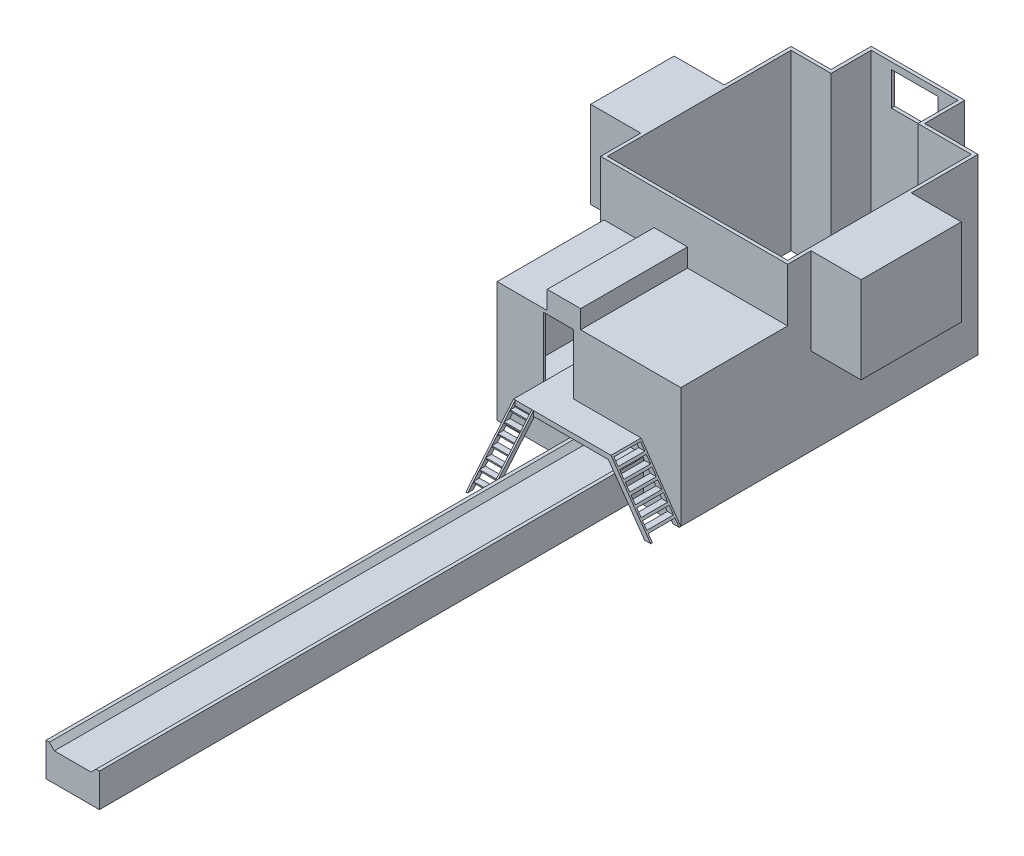
SolidWorks part; units mm, degrees
ref_plane "Alzado" through (0, 0, 0) normal (0, 0, 1) x (1, 0, 0)
ref_plane "Planta" through (0, 0, 0) normal (0, 1, 0) x (1, 0, 0)
ref_plane "Vista lateral" through (0, 0, 0) normal (1, 0, 0) x (0, 0, -1)
sketch "Croquis1" plane through (0, 0, 0) normal (0, 1, 0) x (1, 0, 0)
  line L0 (0, 0) -> (0, 3200)
  line L1 (0, 3200) -> (-100, 3200)
  line L2 (-100, 3200) -> (-100, 4400)
  line L3 (-100, 8900) -> (500, 8900)
  line L4 (500, 8900) -> (1100, 8900)
  line L5 (1100, 8900) -> (1100, 10102.7991)
  line L6 (1100, 10102.7991) -> (3900, 10102.7991)
  line L7 (3900, 8900) -> (5500, 8900)
  line L8 (5500, 8900) -> (5500, 6900)
  line L9 (5500, 0) -> (0, 0)
  line L10 (-100, 4400) -> (-1600, 4400)
  line L11 (-1600, 4400) -> (-1600, 6900)
  line L12 (-1600, 6900) -> (-100, 6900)
  line L13 (-100, 6900) -> (-100, 8900)
  line L14 (5500, 6900) -> (7000, 6900)
  line L15 (7000, 6900) -> (7000, 3900)
  line L16 (7000, 3900) -> (5500, 3900)
  line L17 (5500, 3900) -> (5500, 0)
  line L18 (3900, 10102.7991) -> (3900, 8900)
  dimension "D1" = 5500
  dimension "D2" = 3200
  dimension "D3" = 100
  dimension "D4" = 5700
  dimension "D5" = 1600
  dimension "D6" = 2800
  dimension "D8" = 1200
  dimension "D9" = 2000
  dimension "D10" = 1500
  dimension "D11" = 1500
  dimension "D12" = 2000
  dimension "D13" = 3900
extrude "Saliente-Extruir1" add sketch "Croquis1" along normal blind 5200
sketch "Croquis2" plane through (0, 0, 0) normal (0, 0, 1) x (1, 0, 0)
  line L0 (5500, 5200) -> (5500, 0) construction
  line L1 (0, 5200) -> (5500, 5200)
  line L2 (0, 5200) -> (0, 3600)
  line L3 (0, 3600) -> (5500, 3600)
  line L4 (5500, 5200) -> (5500, 3600)
  dimension "D1" = 1600
extrude "Cortar-Extruir1" cut sketch "Croquis2" against normal up to surface (3200 mm away) up to face at (-50, 2600, -3200)
sketch "Croquis3" plane through (-1600, 0, 0) normal (-1, 0, 0) x (0, 0, 1)
  line L0 (-4400, 5200) -> (-4400, 0) construction
  line L1 (-6900, 0) -> (-4400, 0)
  line L2 (-6900, 0) -> (-6900, 2600)
  line L3 (-6900, 2600) -> (-4400, 2600)
  line L4 (-4400, 0) -> (-4400, 2600)
extrude "Cortar-Extruir2" cut sketch "Croquis3" against normal up to surface (1500 mm away) up to face at (-100, 2600, -3800)
sketch "Croquis4" plane through (7000, 0, 0) normal (1, 0, 0) x (0, 0, -1)
  line L0 (6900, 5200) -> (6900, 0) construction
  line L1 (3900, 0) -> (6900, 0)
  line L2 (3900, 0) -> (3900, 2600)
  line L3 (3900, 2600) -> (6900, 2600)
  line L4 (6900, 0) -> (6900, 2600)
extrude "Cortar-Extruir3" cut sketch "Croquis4" against normal up to surface (1500 mm away) up to face at (5500, 2600, -7900)
sketch "Croquis5" plane through (0, 0, 0) normal (0, 0, 1) x (1, 0, 0)
  line L0 (0, 0) -> (1190.3528, 1700)
  line L1 (1190.3528, 1700) -> (4309.6472, 1700)
  line L2 (4309.6472, 1700) -> (5500, 0)
  line L3 (0, 0) -> (5500, 0) construction
  line L4 (5500, 3600) -> (5500, 0) construction
  line L5 (0, 3600) -> (0, 0) construction
  line L6 (0, 0) -> (183.1162, 0)
  line L7 (183.1162, 0) -> (1268.4379, 1550)
  line L8 (5500, 0) -> (5316.8838, 0)
  line L9 (5316.8838, 0) -> (4231.5621, 1550)
  line L10 (1268.4379, 1550) -> (4231.5621, 1550)
  dimension "D1" = 1700
  dimension "D2" = 35
  dimension "D3" = 35
  dimension "D4" = 150
  dimension "D5" = 150
  dimension "D6" = 150
extrude "Saliente-Extruir2" add sketch "Croquis5" along normal blind 900
sketch "Croquis6" plane through (0, 0, 0) normal (-1, 0, 0) x (0, 0, 1)
  line L0 (900, 0) -> (0, 0) construction
  line L1 (50, 0) -> (850, 0)
  line L2 (50, 0) -> (50, 180)
  line L3 (50, 180) -> (850, 180)
  line L4 (850, 0) -> (850, 180)
  line L5 (900, 1700) -> (900, 0) construction
  line L6 (0, 3600) -> (0, 0) construction
  dimension "D1" = 50
  dimension "D2" = 50
  dimension "D3" = 180
extrude "Cortar-Extruir4" cut sketch "Croquis6" against normal up to surface (5500 mm away) up to face at (5500, 3320, -4580)
sketch "Croquis7" plane through (0, 0, 0) normal (-1, 0, 0) x (0, 0, 1)
  line L0 (50, 180) -> (850, 180) construction
  line L1 (50, 240) -> (850, 240)
  line L2 (50, 240) -> (50, 425)
  line L3 (50, 425) -> (850, 425)
  line L4 (850, 240) -> (850, 425)
  line L6 (50, 485) -> (850, 485)
  line L7 (50, 485) -> (50, 670)
  line L8 (50, 670) -> (850, 670)
  line L9 (850, 485) -> (850, 670)
  line L10 (50, 730) -> (850, 730)
  line L11 (50, 730) -> (50, 915)
  line L12 (50, 915) -> (850, 915)
  line L13 (850, 730) -> (850, 915)
  line L14 (50, 975) -> (850, 975)
  line L15 (50, 975) -> (50, 1160)
  line L16 (50, 1160) -> (850, 1160)
  line L17 (850, 975) -> (850, 1160)
  line L18 (50, 1220) -> (850, 1220)
  line L19 (50, 1220) -> (50, 1405)
  line L20 (50, 1405) -> (850, 1405)
  line L21 (850, 1220) -> (850, 1405)
  line L22 (50, 1465) -> (850, 1465)
  line L23 (50, 1465) -> (50, 1650)
  line L24 (50, 1650) -> (850, 1650)
  line L25 (850, 1465) -> (850, 1650)
  dimension "D1" = 60
  dimension "D2" = 185
  dimension "D3" = 185
  dimension "D4" = 60
  dimension "D5" = 185
  dimension "D6" = 60
  dimension "D7" = 60
  dimension "D8" = 185
  dimension "D9" = 60
  dimension "D10" = 185
  dimension "D11" = 60
  dimension "D12" = 185
extrude "Cortar-Extruir5" cut sketch "Croquis7" against normal up to surface (5500 mm away) up to face at (5500, 3320, -4580)
sketch "Croquis8" plane through (0, 0, 0) normal (0, 0, 1) x (1, 0, 0)
  line L0 (4309.6472, 1700) -> (1190.3528, 1700) construction
  line L1 (1390.3528, 1700) -> (2290.3528, 1700)
  line L2 (1390.3528, 1700) -> (1390.3528, 3500)
  line L3 (1390.3528, 3500) -> (2290.3528, 3500)
  line L4 (2290.3528, 1700) -> (2290.3528, 3500)
  dimension "D1" = 1800
  dimension "D2" = 200
  dimension "D3" = 900
extrude "Cortar-Extruir6" cut sketch "Croquis8" against normal up to surface (3200 mm away) up to face at (1800, 2933.3333, -3200)
sketch "Croquis9" plane through (0, 0, 0) normal (0, -1, 0) x (1, 0, 0)
  line L0 (0, -3200) -> (0, 0) construction
  line L1 (50.8, -3149.2) -> (5449.2, -3149.2)
  line L2 (50.8, -3149.2) -> (50.8, -51.6)
  line L3 (50.8, -51.6) -> (5449.2, -51.6)
  line L4 (5449.2, -3149.2) -> (5449.2, -51.6)
  line L5 (183.1162, 50) -> (0, 50) construction
  line L6 (5500, 0) -> (5500, -8900) construction
  dimension "D1" = 50.8
  dimension "D2" = 101.6
  dimension "D3" = 50.8
  dimension "D4" = 50.8
extrude "Cortar-Extruir7" cut sketch "Croquis9" against normal blind 3500
sketch "Croquis10" plane through (0, 0, 900) normal (0, 0, 1) x (1, 0, 0)
  line L1 (1390.3528, 1700) -> (2290.3528, 1700)
  line L2 (1390.3528, 1700) -> (1390.3528, 1600)
  line L3 (1390.3528, 1600) -> (2290.3528, 1600)
  line L4 (2290.3528, 1700) -> (2290.3528, 1600)
  dimension "D1" = 100
extrude "Saliente-Extruir3" add sketch "Croquis10" against normal up to surface (4049.2 mm away) up to face at (2295.1764, 2175, -3149.2)
sketch "Croquis11" plane through (0, 0, 0) normal (0, 0, 1) x (1, 0, 0)
  line L0 (183.1162, 0) -> (5316.8838, 0) construction
  line L1 (2190, 0) -> (4390, 0)
  line L2 (2190, 0) -> (2190, 1300)
  line L3 (2190, 1300) -> (4390, 1300)
  line L4 (4390, 0) -> (4390, 1300)
  line L5 (5500, 3600) -> (5500, 0) construction
  dimension "D1" = 1110
  dimension "D2" = 2200
  dimension "D3" = 1300
extrude "Cortar-Extruir8" cut sketch "Croquis11" against normal up to surface (3149.2 mm away) up to face at (2204.2117, 2060, -3149.2)
sketch "Croquis12" plane through (0, 0, 0) normal (0, -1, 0) x (1, 0, 0)
  line L0 (50.8, -51.6) -> (50.8, -3149.2) construction
  line L1 (50.8, -1849.2) -> (5449.2, -1849.2)
  line L2 (50.8, -1849.2) -> (50.8, -549.2)
  line L3 (50.8, -549.2) -> (5449.2, -549.2)
  line L4 (5449.2, -1849.2) -> (5449.2, -549.2)
  line L5 (5449.2, -3149.2) -> (5449.2, -51.6) construction
  line L6 (50.8, -3149.2) -> (5449.2, -3149.2) construction
  dimension "D1" = 1300
  dimension "D2" = 1300
extrude "Saliente-Extruir4" add sketch "Croquis12" against normal blind 1000
sketch "Croquis13" plane through (0, 0, 0) normal (0, -1, 0) x (1, 0, 0)
  line L0 (50.8, -3149.2) -> (5449.2, -3149.2) construction
  line L1 (50.8, -1849.2) -> (1150.8, -1849.2)
  line L2 (50.8, -1849.2) -> (50.8, -3149.2)
  line L3 (50.8, -3149.2) -> (1150.8, -3149.2)
  line L4 (1150.8, -1849.2) -> (1150.8, -3149.2)
  line L5 (50.8, -1849.2) -> (5449.2, -1849.2) construction
  line L6 (5449.2, -3149.2) -> (4349.2, -3149.2)
  line L7 (5449.2, -3149.2) -> (5449.2, -1849.2)
  line L8 (5449.2, -1849.2) -> (4349.2, -1849.2)
  line L9 (4349.2, -3149.2) -> (4349.2, -1849.2)
  dimension "D1" = 1100
  dimension "D2" = 1100
extrude "Saliente-Extruir5" add sketch "Croquis13" against normal blind 1000
sketch "Croquis14" plane through (0, 0, -549.2) normal (0, 0, 1) x (1, 0, 0)
  line L0 (5449.2, 1000) -> (50.8, 1000) construction
  line L1 (2540, 1000) -> (4140, 1000)
  line L2 (2540, 1000) -> (2540, 0)
  line L3 (2540, 0) -> (4140, 0)
  line L4 (4140, 1000) -> (4140, 0)
  line L5 (5449.2, 0) -> (50.8, 0) construction
  line L6 (2190, 1300) -> (2190, 0) construction
  dimension "D1" = 1600
  dimension "D2" = 350
extrude "Saliente-Extruir6" add sketch "Croquis14" along normal blind 16600
sketch "Croquis18" plane through (0, 0, 16050.8) normal (0, 0, 1) x (1, 0, 0)
  line L0 (2640, 1000) -> (2790, 850)
  line L1 (4140, 1000) -> (2540, 1000) construction
  line L2 (2790, 850) -> (3890, 850)
  line L3 (3890, 850) -> (4040, 1000)
  line L4 (4040, 1000) -> (2640, 1000)
  line L5 (2540, 1000) -> (2540, 0) construction
  line L6 (4140, 0) -> (4140, 1000) construction
  dimension "D1" = 100
  dimension "D2" = 100
  dimension "D3" = 150
  dimension "D4" = 45
  dimension "D5" = 45
extrude "Cortar-Extruir13" cut sketch "Croquis18" against normal up to surface (16600 mm away) up to face at (4794.6, 500, -549.2)
chamfer "Chaflán1" distance 150 angle 45 1 edges at (3340, 1000, -549.2)
sketch "Croquis21" plane through (0, 0, 0) normal (0, -1, 0) x (1, 0, 0)
  line L0 (3800, -10002.7991) -> (1200, -10002.7991)
  line L1 (1200, -10002.7991) -> (1200, -8800)
  line L2 (0, -8800) -> (0, -3300)
  line L3 (0, -3300) -> (5400, -3300)
  line L4 (5400, -3300) -> (5400, -8800)
  line L5 (5400, -8800) -> (3800, -8800)
  line L6 (3800, -8800) -> (3800, -10002.7991)
  line L7 (1200, -8800) -> (0, -8800)
  line L8 (1100, -8900) -> (-100, -8900) construction
  line L9 (-100, -8900) -> (-100, -3200) construction
  line L10 (1100, -10102.7991) -> (1100, -8900) construction
  line L11 (-100, -3200) -> (0, -3200) construction
  line L12 (5500, 0) -> (5500, -8900) construction
  line L13 (5500, -8900) -> (3900, -8900) construction
  line L14 (3900, -8900) -> (3900, -10102.7991) construction
  line L15 (3900, -10102.7991) -> (1100, -10102.7991) construction
  dimension "D1" = 100
  dimension "D2" = 100
  dimension "D3" = 100
  dimension "D4" = 100
  dimension "D5" = 100
  dimension "D6" = 100
  dimension "D7" = 100
  dimension "D8" = 100
extrude "Cortar-Extruir14" cut sketch "Croquis21" against normal blind 5400
sketch "Croquis22" plane through (0, 0, 0) normal (0, 0, 1) x (1, 0, 0)
  line L0 (0, 3600) -> (5500, 3600) construction
  line L1 (1500, 3600) -> (2500, 3600)
  line L2 (1500, 3600) -> (1500, 4150)
  line L3 (1500, 4150) -> (2500, 4150)
  line L4 (2500, 3600) -> (2500, 4150)
  line L5 (0, 3600) -> (0, 0) construction
  dimension "D1" = 1500
  dimension "D2" = 1000
  dimension "D3" = 550
extrude "Saliente-Extruir7" add sketch "Croquis22" against normal up to surface (3200 mm away) up to face at (1800, 2933.3333, -3200)
sketch "Croquis23" plane through (0, 0, 900) normal (0, 0, 1) x (1, 0, 0)
  line L1 (0, 0) -> (1390.3528, 0)
  line L2 (0, 0) -> (0, 1700)
  line L3 (0, 1700) -> (1390.3528, 1700)
  line L4 (1390.3528, 0) -> (1390.3528, 1700)
extrude "Cortar-Extruir15" cut sketch "Croquis23" against normal up to surface (900 mm away) up to face at (3020, 712.5, 0)
sketch "Croquis24" plane through (1390.3528, 0, 0) normal (-1, 0, 0) x (0, 0, 1)
  line L0 (900, 1700) -> (2326.4694, 0)
  line L1 (16050.8, 0) -> (-549.2, 0) construction
  line L2 (900, 1700) -> (900, 1502.4231)
  line L3 (900, 1550) -> (900, 0) construction
  line L4 (900, 1502.4231) -> (2160.6826, 0)
  line L5 (2160.6826, 0) -> (2326.4694, 0)
  dimension "D1" = 50
  dimension "D2" = 127
extrude "Saliente-Extruir8" add sketch "Croquis24" against normal blind 600
sketch "Croquis25" plane through (0, 1700, 0) normal (0, 1, 0) x (1, 0, 0)
  line L0 (1990.3528, -900) -> (1390.3528, -900) construction
  line L1 (1441.1528, -900) -> (1939.5528, -900)
  line L2 (1441.1528, -900) -> (1441.1528, -2326.4694)
  line L3 (1441.1528, -2326.4694) -> (1939.5528, -2326.4694)
  line L4 (1939.5528, -900) -> (1939.5528, -2326.4694)
  line L5 (1990.3528, -2326.4694) -> (1390.3528, -2326.4694) construction
  line L6 (1390.3528, -2326.4694) -> (1390.3528, -900) construction
  line L7 (1990.3528, -2326.4694) -> (1990.3528, -900) construction
  dimension "D1" = 50.8
  dimension "D2" = 50.8
extrude "Cortar-Extruir16" cut sketch "Croquis25" against normal up to surface (1700 mm away) up to face at (5408.4419, 0, 875)
sketch "Croquis26" plane through (1390.3528, 0, 0) normal (-1, 0, 0) x (0, 0, 1)
  line L0 (2326.4694, 0) -> (900, 1700) construction
  line L1 (1051.0379, 1520) -> (900, 1520)
  line L2 (1051.0379, 1520) -> (1051.0379, 1481.9)
  line L3 (1051.0379, 1481.9) -> (900, 1481.9)
  line L4 (900, 1520) -> (900, 1481.9)
  line L5 (900, 1550) -> (900, 0) construction
  line L6 (0, 1700) -> (900, 1700) construction
  line L8 (1234.0456, 1301.9) -> (1059.0456, 1301.9)
  line L9 (1234.0456, 1301.9) -> (1234.0456, 1263.8)
  line L10 (1234.0456, 1263.8) -> (1059.0456, 1263.8)
  line L11 (1059.0456, 1301.9) -> (1059.0456, 1263.8)
  line L12 (1417.0532, 1083.8) -> (1242.0532, 1083.8)
  line L13 (1417.0532, 1083.8) -> (1417.0532, 1045.7)
  line L14 (1417.0532, 1045.7) -> (1242.0532, 1045.7)
  line L15 (1242.0532, 1083.8) -> (1242.0532, 1045.7)
  line L16 (1600.0608, 865.7) -> (1425.0608, 865.7)
  line L17 (1600.0608, 865.7) -> (1600.0608, 827.6)
  line L18 (1600.0608, 827.6) -> (1425.0608, 827.6)
  line L19 (1425.0608, 865.7) -> (1425.0608, 827.6)
  line L20 (1783.0685, 647.6) -> (1608.0685, 647.6)
  line L21 (1783.0685, 647.6) -> (1783.0685, 609.5)
  line L22 (1783.0685, 609.5) -> (1608.0685, 609.5)
  line L23 (1608.0685, 647.6) -> (1608.0685, 609.5)
  line L24 (1966.0761, 429.5) -> (1791.0761, 429.5)
  line L25 (1966.0761, 429.5) -> (1966.0761, 391.4)
  line L26 (1966.0761, 391.4) -> (1791.0761, 391.4)
  line L27 (1791.0761, 429.5) -> (1791.0761, 391.4)
  line L28 (2149.0837, 211.4) -> (1974.0837, 211.4)
  line L29 (2149.0837, 211.4) -> (2149.0837, 173.3)
  line L30 (2149.0837, 173.3) -> (1974.0837, 173.3)
  line L31 (1974.0837, 211.4) -> (1974.0837, 173.3)
  dimension "D1" = 180
  dimension "D2" = 38.1
  dimension "D3" = 180
  dimension "D4" = 175
  dimension "D5" = 38.1
  dimension "D6" = 180
  dimension "D7" = 175
  dimension "D8" = 38.1
  dimension "D9" = 180
  dimension "D10" = 175
  dimension "D11" = 38.1
  dimension "D12" = 180
  dimension "D13" = 175
  dimension "D14" = 38.1
  dimension "D15" = 180
  dimension "D16" = 175
  dimension "D17" = 38.1
  dimension "D18" = 180
  dimension "D19" = 175
  dimension "D20" = 38.1
extrude "Saliente-Extruir9" add sketch "Croquis26" against normal up to surface (549.2 mm away) up to face at (1939.5528, 950.4846, 1437.4304)
sketch "Croquis27" plane through (0, 0, -10102.7991) normal (0, 0, -1) x (-1, 0, 0)
  line L0 (-2500, 5200) -> (-2500, 4000) construction
  line L1 (-3900, 5200) -> (-1100, 5200) construction
  line L2 (-2500, 4000) -> (-3200, 4000)
  line L3 (-3200, 4000) -> (-3200, 5000)
  line L4 (-3200, 5000) -> (-1800, 5000)
  line L5 (-1800, 5000) -> (-1800, 4000)
  line L6 (-1800, 4000) -> (-2500, 4000)
  dimension "D1" = 1200
  dimension "D2" = 700
  dimension "D3" = 700
  dimension "D4" = 1000
extrude "Cortar-Extruir17" cut sketch "Croquis27" against normal up to surface (100 mm away) up to face at (2500, 2600, -10002.7991)
